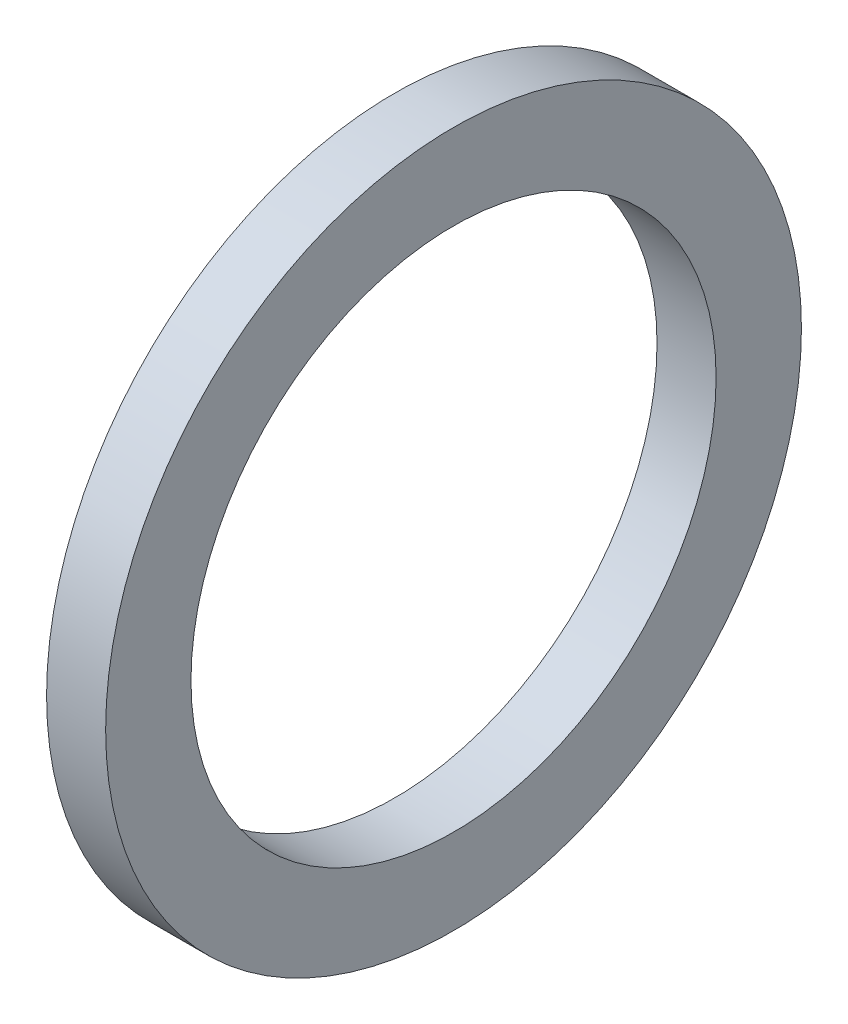
SolidWorks part; units mm, degrees
material "6061 Alloy"
ref_plane "Front Plane" through (0, 0, 0) normal (0, 0, 1) x (1, 0, 0)
ref_plane "Top Plane" through (0, 0, 0) normal (0, 1, 0) x (1, 0, 0)
ref_plane "Right Plane" through (0, 0, 0) normal (1, 0, 0) x (0, 0, -1)
sketch "Sketch1" plane through (0, 0, 0) normal (1, 0, 0) x (0, 0, -1)
  circle A0 centre (0, 0) radius 4
  circle A1 centre (0, 0) radius 5.3
  dimension "D1" = 10.6
  dimension "D2" = 8
extrude "Boss-Extrude1" add sketch "Sketch1" along normal mid plane 0.9
